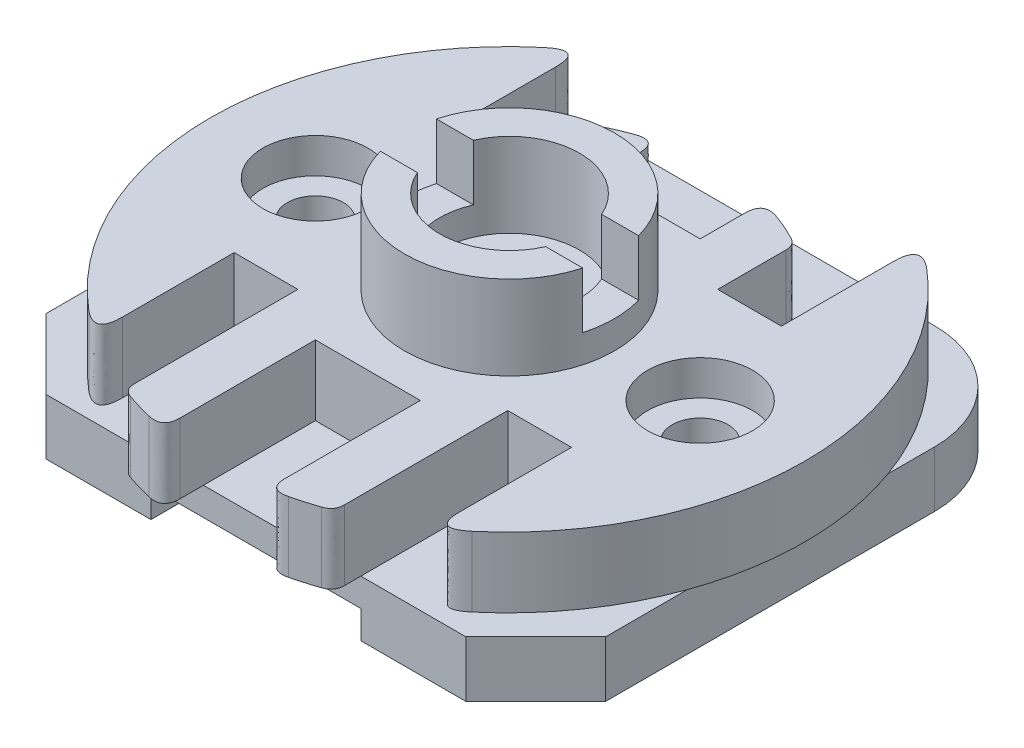
SolidWorks part; units mm, degrees
material "AISI 1020"
ref_plane "Front Plane" through (0, 0, 0) normal (0, 0, 1) x (1, 0, 0)
ref_plane "Top Plane" through (0, 0, 0) normal (0, 1, 0) x (1, 0, 0)
ref_plane "Right Plane" through (0, 0, 0) normal (1, 0, 0) x (0, 0, -1)
sketch "Sketch2" plane through (0, 0, 0) normal (0, 1, 0) x (1, 0, 0)
  line L1 (0, 0) -> (80, 0)
  line L2 (0, 0) -> (0, 72)
  line L3 (0, 72) -> (80, 72)
  line L4 (80, 0) -> (80, 72)
  dimension "A" = 80
  dimension "B" = 72
extrude "Boss-Extrude1" add sketch "Sketch2" along normal blind 8
sketch "Sketch3" plane through (0, 8, 0) normal (0, 1, 0) x (1, 0, 0)
  line L0 (0, 36) -> (80, 36) construction
  line L1 (0, 72) -> (0, 0) construction
  line L2 (80, 0) -> (80, 72) construction
  line L3 (40, 16) -> (40, 56) construction
  line L6 (32.5, 65.0474) -> (32.5, 56)
  line L7 (32.5, 56) -> (47.5, 56)
  line L8 (47.5, 56) -> (47.5, 65.0474)
  line L9 (25, 61.9808) -> (25, 51)
  line L10 (25, 51) -> (15.8909, 51)
  line L11 (15.8909, 51) -> (15.8909, 71)
  line L12 (55, 61.9808) -> (55, 51)
  line L13 (55, 51) -> (64.1091, 51)
  line L14 (64.1091, 51) -> (64.1091, 71)
  line L15 (25, -3.7649) -> (25, 21)
  line L16 (15.8909, 21) -> (15.8909, 1)
  line L17 (25, 21) -> (15.8909, 21)
  line L18 (32.5, -5.833) -> (32.5, 16)
  line L19 (32.5, 16) -> (47.5, 16)
  line L20 (47.5, 16) -> (47.5, -5.833)
  line L21 (64.1091, 21) -> (64.1091, 1)
  line L22 (55, 21) -> (64.1091, 21)
  line L23 (55, -3.7649) -> (55, 21)
  arc A0 (15.8909, 71) -> (15.8909, 1) centre (40, 36) ccw
  arc A3 (64.1091, 1) -> (64.1091, 71) centre (40, 36) ccw
  arc A4 (47.5, -5.833) -> (55, -3.7649) centre (40, 36) ccw
  arc A5 (25, -3.7649) -> (32.5, -5.833) centre (40, 36) ccw
  arc A6 (25, 61.9808) -> (32.5, 65.0474) centre (40, 36) cw
  arc A7 (47.5, 65.0474) -> (55, 61.9808) centre (40, 36) cw
  point P19 (40, 36)
  dimension "D1" = 15
  dimension "DIA" = 85
  dimension "D4" = 30
  dimension "D2" = 15
  dimension "D3" = 20
  dimension "E1" = 15
  dimension "D5" = 20
extrude "Boss-Extrude2" add sketch "Sketch3" along normal blind 10 contours A4 L23 L22 L21 A3 L14 L13 L12 A7 L8 L7 L6 A6 L9 L10 L11 A0 L16 L17 L15 A5 L18 L19 L20
chamfer "Chamfer1" distance 10 angle 45 2 edges at (0, 4, 0) (80, 4, 0)
fillet "Fillet1" radius 15 2 edges at (80, 4, -72) (0, 4, -72)
sketch "Sketch4" plane through (0, 18, 0) normal (0, 1, 0) x (1, 0, 0)
  line L0 (-2.5, 36) -> (82.5, 36) construction
  line L2 (40, 56) -> (40, 16) construction
  line L3 (32.5, 16) -> (47.5, 16) construction
  line L4 (32.5, 56) -> (47.5, 56) construction
  circle A0 centre (40.2538, 36) radius 15
  arc A1 (15.8909, 71) -> (15.8909, 1) centre (40, 36) ccw construction
  arc A2 (64.1091, 1) -> (64.1091, 71) centre (40, 36) ccw construction
  circle A3 centre (40.2538, 36) radius 10
  dimension "DiaUP" = 30
  dimension "T1" = 5
extrude "Boss-Extrude3" add sketch "Sketch4" along normal blind 12
sketch "Sketch5" plane through (0, 0, 0) normal (1, 0, 0) x (0, 0, -1)
  line L0 (36, 30) -> (36, 8) construction
  line L1 (51, 30) -> (21, 30) construction
  line L2 (21.6386, 8) -> (50.3614, 8) construction
  line L3 (46, 30) -> (26, 30) construction
  line L4 (32, 30) -> (40, 30)
  line L5 (32, 30) -> (32, 22)
  line L6 (32, 22) -> (40, 22)
  line L7 (40, 30) -> (40, 22)
  dimension "D1" = 8
  dimension "D2" = 8
extrude "Cut-Extrude1" cut sketch "Sketch5" along normal through all contours L7 L6 L5 L4
hole_wizard "CBORE for M10 Hex Head Bolt1" positions "Sketch6" profile "Sketch7" counterbore size "M10" standard "ANSI Metric" end condition through all
sketch "Sketch6" plane through (0, 18, 0) normal (0, 1, 0) x (1, 0, 0)
  line L0 (82.5, 36) -> (-2.5, 36) construction
  line L2 (40, 16) -> (40, 56) construction
  line L3 (32.5, 16) -> (47.5, 16) construction
  line L4 (32.5, 56) -> (47.5, 56) construction
  arc A0 (64.1091, 1) -> (64.1091, 71) centre (40, 36) ccw construction
  arc A1 (15.8909, 71) -> (15.8909, 1) centre (40, 36) ccw construction
  point P0 (67.5, 36)
  point P2 (12.5, 36)
  dimension "HoleD" = 55
sketch "Sketch7" plane through (67.5, 18, -36) normal (1, 0, 0) x (0, 0, 1)
  line L0 (0, 0) -> (0, 18)
  line L1 (0, 18) -> (4, 18)
  line L3 (4, 18) -> (4, 5)
  line L4 (4, 5) -> (7.5, 5)
  line L5 (7.5, 5) -> (7.5, 0)
  line L7 (7.5, 0) -> (0, 0)
  line L11 (0, -6.35) -> (0, 107.95) construction
  dimension "Thru Hole Dia." = 8
  dimension "Thru Hole Depth" = 18
  dimension "C'Bore Dia." = 15
  dimension "C'Bore Depth" = 5
sketch "Sketch8" plane through (0, 0, -72) normal (0, 0, -1) x (-1, 0, 0)
  line L0 (-65, 0) -> (-15, 0) construction
  line L1 (-55, 0) -> (-25, 0)
  line L2 (-55, 0) -> (-55, 4)
  line L3 (-55, 4) -> (-25, 4)
  line L4 (-25, 0) -> (-25, 4)
  line L5 (-25, 18) -> (-25, 8) construction
  line L7 (-55, 18) -> (-55, 8) construction
  dimension "D1" = 4
extrude "Cut-Extrude2" cut sketch "Sketch8" against normal through all
fillet "Fillet2" radius 2 12 edges at (64.1091, 13, -71) (15.8909, 13, -71) (15.8909, 13, -1) (64.1091, 13, -1) (55, 13, 3.7649) (47.5, 13, 5.833) (32.5, 13, 5.833) (25, 13, 3.7649) (55, 13, -61.9808) (47.5, 13, -65.0474) (32.5, 13, -65.0474) (25, 13, -61.9808) conic rho 0.5
